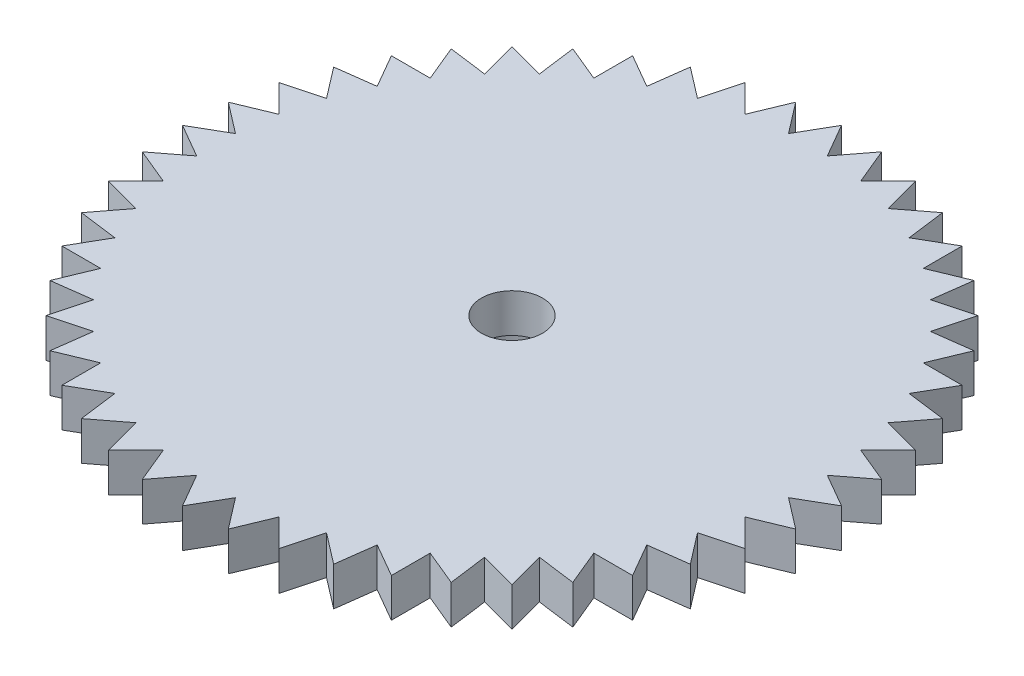
SolidWorks part; units mm, degrees
ref_plane "Front Plane" through (0, 0, 0) normal (0, 0, 1) x (1, 0, 0)
ref_plane "Top Plane" through (0, 0, 0) normal (0, 1, 0) x (1, 0, 0)
ref_plane "Right Plane" through (0, 0, 0) normal (1, 0, 0) x (0, 0, -1)
sketch "Sketch1" plane through (0, 0, 0) normal (0, 1, 0) x (1, 0, 0)
  circle A1 centre (0, 0) radius 15.24
  dimension "D2" = 30.48
extrude "Boss-Extrude1" add sketch "Sketch1" along normal blind 5.08
sketch "Sketch3" plane through (0, 5.08, 0) normal (0, 1, 0) x (1, 0, 0)
  line L0 (0, 0) -> (0, 21.59) construction
  line L1 (0, 21.59) -> (3.97, 14.7138)
  line L2 (0, 21.59) -> (-3.97, 14.7138)
  line L3 (3.97, 14.7138) -> (-3.97, 14.7138)
  circle A0 centre (0, 0) radius 15.24 construction
  dimension "D1" = 21.59
  dimension "D2" = 30
  dimension "D3" = 30
extrude "Boss-Extrude3" add sketch "Sketch3" against normal blind 2.54
ref_axis "Axis1" through (0, -0.127, 0) along (0, 1, 0)
pattern_circular "CirPattern1" count 48 every 7.5 about axis through (0, -0.127, 0) along (0, 1, 0) of "Boss-Extrude3"
sketch "Sketch6" plane through (0, 0, 0) normal (0, -1, 0) x (1, 0, 0)
  circle A0 centre (0, 0) radius 4.064
  dimension "D1" = 8.128
extrude "Cut-Extrude1" cut sketch "Sketch6" against normal blind 2.54
sketch "Sketch7" plane through (0, 5.08, 0) normal (0, 1, 0) x (1, 0, 0)
  circle A0 centre (0, 0) radius 2
  dimension "D1" = 4
extrude "Cut-Extrude2" cut sketch "Sketch7" against normal blind 2.54 contours A0
